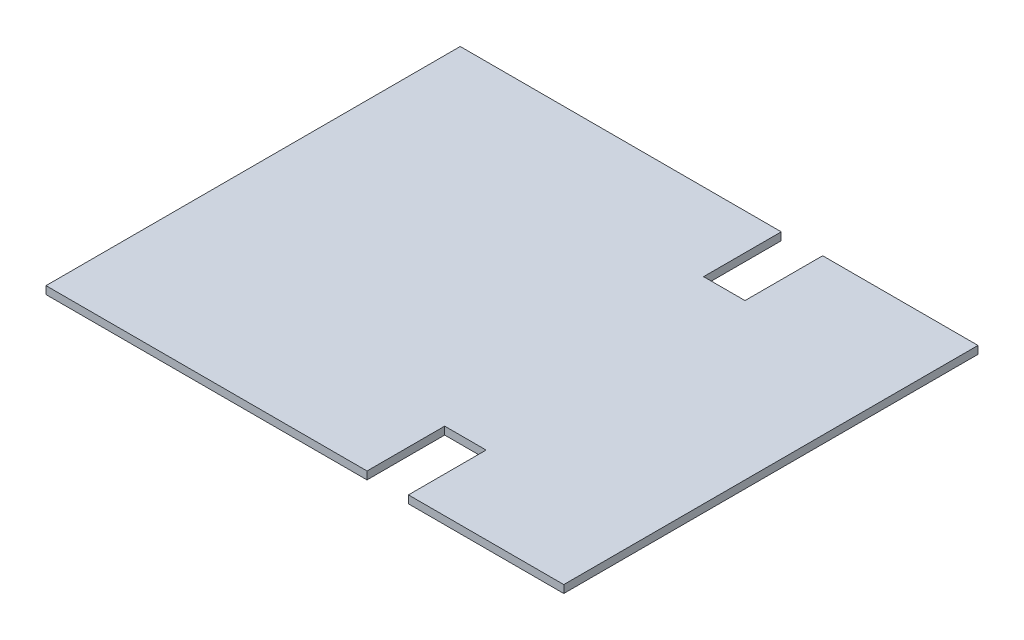
SolidWorks part; units mm, degrees
ref_plane "Front Plane" through (0, 0, 0) normal (0, 0, 1) x (1, 0, 0)
ref_plane "Top Plane" through (0, 0, 0) normal (0, 1, 0) x (1, 0, 0)
ref_plane "Right Plane" through (0, 0, 0) normal (1, 0, 0) x (0, 0, -1)
sketch "Sketch1" plane through (0, 0, 0) normal (0, 1, 0) x (1, 0, 0)
  line L1 (0, 0) -> (100, 0)
  line L2 (0, 0) -> (0, 80)
  line L3 (0, 80) -> (100, 80)
  line L4 (100, 0) -> (100, 80)
  dimension "D1" = 80
  dimension "D2" = 100
extrude "Boss-Extrude1" add sketch "Sketch1" along normal blind 1.5
sketch "Sketch2" plane through (0, 1.5, 0) normal (0, 1, 0) x (1, 0, 0)
  line L0 (100, 80) -> (0, 80) construction
  line L1 (62, 80) -> (70, 80)
  line L2 (62, 80) -> (62, 65)
  line L3 (62, 65) -> (70, 65)
  line L4 (70, 80) -> (70, 65)
  line L5 (0, 0) -> (100, 0) construction
  line L6 (62, 0) -> (70, 0)
  line L7 (62, 0) -> (62, 15)
  line L8 (62, 15) -> (70, 15)
  line L9 (70, 0) -> (70, 15)
  line L10 (100, 0) -> (100, 80) construction
  dimension "D1" = 30
  dimension "D2" = 15
  dimension "D3" = 8
extrude "Cut-Extrude1" cut sketch "Sketch2" against normal up to next
